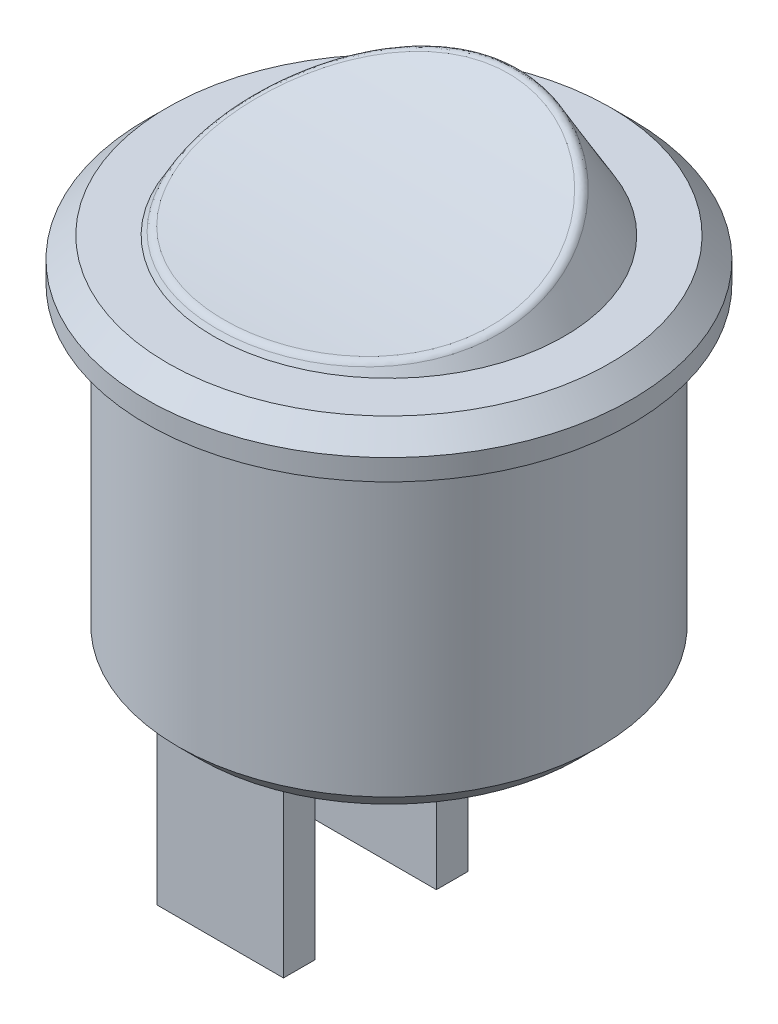
SolidWorks part; units mm, degrees
ref_plane "Front Plane" through (0, 0, 0) normal (0, 0, 1) x (1, 0, 0)
ref_plane "Top Plane" through (0, 0, 0) normal (0, 1, 0) x (1, 0, 0)
ref_plane "Right Plane" through (0, 0, 0) normal (1, 0, 0) x (0, 0, -1)
sketch "Sketch2" plane through (0, 0, 0) normal (1, 0, 0) x (0, 0, -1)
  line L0 (0, 0) -> (0, 17)
  line L1 (0, 17) -> (10.5, 17)
  line L2 (10.5, 17) -> (11.5, 16)
  line L3 (11.5, 16) -> (11.5, 15)
  line L4 (11.5, 15) -> (10, 15)
  line L5 (10, 15) -> (10, 0)
  line L6 (10, 0) -> (0, 0)
  dimension "D1" = 10
  dimension "D2" = 17
  dimension "D3" = 11.5
  dimension "D4" = 2
  dimension "D5" = 135
  dimension "D6" = 1
revolve "Revolve1" add sketch "Sketch2" angle 360 about L0
sketch "Sketch3" plane through (0, 17, 0) normal (0, 1, 0) x (1, 0, 0)
  circle A0 centre (0, 0) radius 9
  dimension "D1" = 18
extrude "Boss-Extrude1" add sketch "Sketch3" along normal blind 4
chamfer "Chamfer1" distance 3 angle 60 1 edges at (0, 21, 9) first distance on face at (0, 21, 9)
sketch "Sketch5" plane through (0, 0, 0) normal (1, 0, 0) x (0, 0, -1)
  line L0 (6, 21) -> (-6, 21) construction
  line L2 (6, 21) -> (-6, 21)
  line L3 (-6, 21) -> (-8.0855, 17.4422)
  arc A0 (-8.0855, 17.4422) -> (6, 21) centre (-8.0851, 47.1023) ccw
extrude "Cut-Extrude2" cut sketch "Sketch5" against normal through all both and the other way through all
fillet "Fillet1" radius 0.4 1 edges at (7.0333, 17.8022, 3.478)
sketch "Sketch6" plane through (0, 15, 0) normal (0, -1, 0) x (1, 0, 0)
  line L0 (-10.4749, 0) -> (0, 0) construction
  line L1 (-9.9499, -1) -> (-11, -1)
  line L2 (-9.9499, -1) -> (-9.9499, 1)
  line L3 (-9.9499, 1) -> (-11, 1)
  line L4 (-11, -1) -> (-11, 1)
  line L5 (-9.9499, -1) -> (-11, 1) construction
  line L6 (-9.9499, 1) -> (-11, -1) construction
  circle A0 centre (0, 0) radius 10 construction
  point P0 (-10.4749, 0)
  dimension "D1" = 2
  dimension "D2" = 11
extrude "Boss-Extrude2" add sketch "Sketch6" along normal blind 3
sketch "Sketch7" plane through (0, 0, 0) normal (0, -1, 0) x (1, 0, 0)
  line L0 (0, 0) -> (0, 8) construction
  line L2 (-3, 0.75) -> (3, 0.75)
  line L3 (-3, 8) -> (3, 8)
  line L4 (-3, 8) -> (-3, 6.5)
  line L5 (-3, 6.5) -> (3, 6.5)
  line L6 (3, 8) -> (3, 6.5)
  line L7 (-3, 8) -> (3, 6.5) construction
  line L8 (-3, 6.5) -> (3, 8) construction
  line L9 (-3, 0.75) -> (-3, -0.75)
  line L10 (-3, -0.75) -> (3, -0.75)
  line L11 (3, 0.75) -> (3, -0.75)
  line L12 (-3, 0.75) -> (3, -0.75) construction
  line L13 (-3, -0.75) -> (3, 0.75) construction
  point P11 (3, 7.508)
  dimension "D1" = 6
  dimension "D2" = 1.5
  dimension "D3" = 8
extrude "Boss-Extrude3" add sketch "Sketch7" along normal blind 8
chamfer "Chamfer2" distance 1 angle 45 1 edges at (0, 0, -10)
